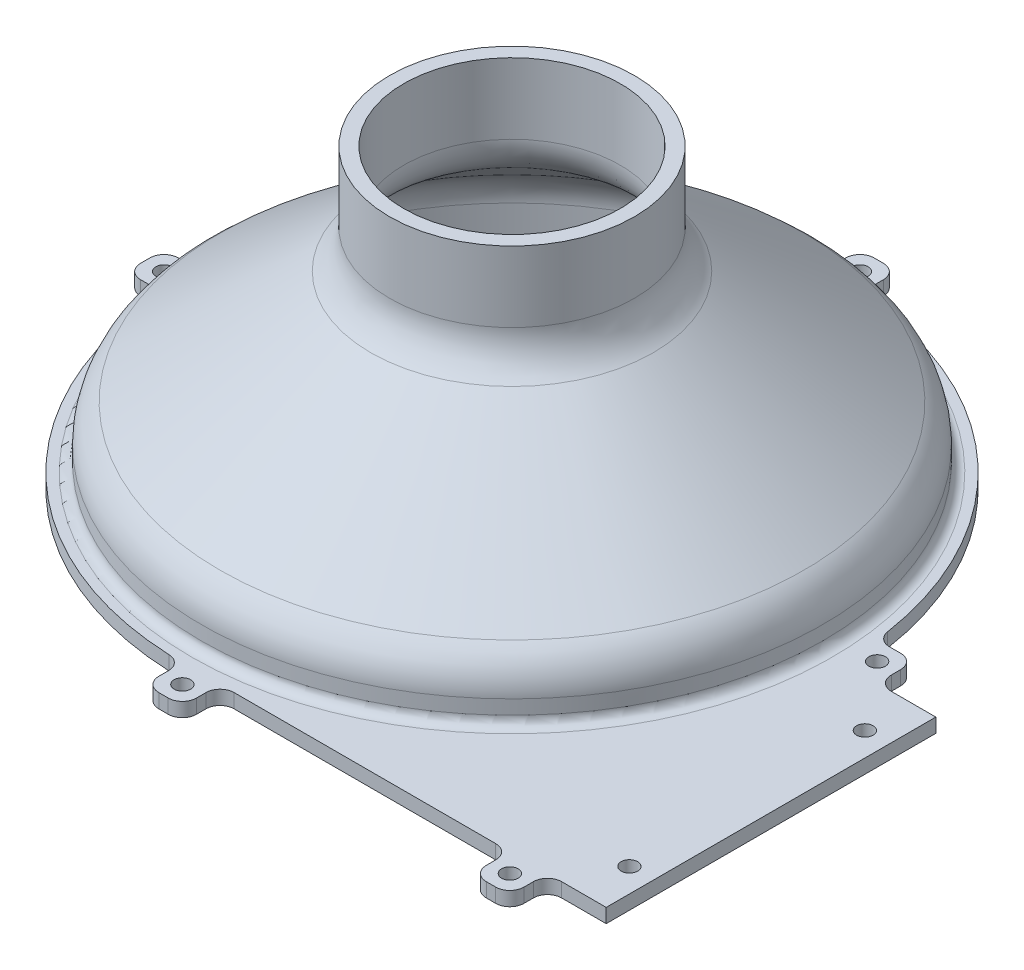
SolidWorks part; units mm, degrees
ref_plane "Front Plane" through (0, 0, 0) normal (0, 0, 1) x (1, 0, 0)
ref_plane "Top Plane" through (0, 0, 0) normal (0, 1, 0) x (1, 0, 0)
ref_plane "Right Plane" through (0, 0, 0) normal (1, 0, 0) x (0, 0, -1)
sketch "Sketch2" plane through (0, 0, 0) normal (0, 1, 0) x (1, 0, 0)
  line L0 (70, 0) -> (70, -70) construction
  line L1 (0, -70) -> (90, -70)
  line L3 (70, 0) -> (90, 0)
  line L4 (90, -70) -> (90, 0)
  arc A0 (70, 0) -> (0, -70) centre (0, 0) ccw
  circle A1 centre (0, 0) radius 63
  dimension "D1" = 140
  dimension "D4" = 126
  dimension "D3" = 20
extrude "Boss-Extrude1" add sketch "Sketch2" along normal blind 3
sketch "Sketch3" plane through (0, 3, 0) normal (0, 1, 0) x (1, 0, 0)
  circle A2 centre (0, 0) radius 63 construction
  circle A3 centre (0, 0) radius 63
  circle A4 centre (0, 0) radius 66
  dimension "D1" = 3
extrude "Boss-Extrude2" add sketch "Sketch3" along normal blind 10
sketch "Sketch6" plane through (0, 0, 0) normal (1, 0, 0) x (0, 0, -1)
  line L0 (-66, 13) -> (-26, 43)
  line L1 (-26, 43) -> (-23, 43)
  line L2 (-23, 43) -> (-63, 13)
  line L3 (66, 13) -> (-66, 13) construction
  line L4 (-66, 13) -> (-63, 13)
  line L5 (0, 0) -> (0, 43) construction
  line L6 (-70, 0) -> (70, 0) construction
  line L7 (-23, 43) -> (0, 43) construction
  dimension "D1" = 3
  dimension "D2" = 30
  dimension "D3" = 26
revolve "Revolve1" add sketch "Sketch6" angle 360 about L5
sketch "Sketch7" plane through (0, 43, 0) normal (0, 1, 0) x (1, 0, 0)
  circle A0 centre (0, 0) radius 26
  circle A1 centre (0, 0) radius 23
  circle A2 centre (0, 0) radius 23 construction
  circle A3 centre (0, 0) radius 26 construction
extrude "Boss-Extrude3" add sketch "Sketch7" along normal blind 20
fillet "Fillet1" radius 10 4 edges at (0, 43, -23) (0, 13, -63) (0, 13, 66) (0, 43, 26)
fillet "Fillet2" radius 2 1 edges at (0, 3, 66)
sketch "Sketch8" plane through (0, 0, 0) normal (0, -1, 0) x (1, 0, 0)
  line L21 (90, 0) -> (70, 0) construction
  line L22 (77.5414, 0) -> (69.5414, 0)
  line L23 (77.5414, 0) -> (77.5414, -8)
  line L24 (77.5414, -8) -> (69.5414, -8)
  line L25 (69.5414, 0) -> (69.5414, -8)
  line L26 (73.5414, 0) -> (73.5414, -8) construction
  line L27 (0, 70) -> (90, 70) construction
  line L28 (77.5414, 70) -> (69.5414, 70)
  line L29 (77.5414, 70) -> (77.5414, 78)
  line L30 (77.5414, 78) -> (69.5414, 78)
  line L31 (69.5414, 70) -> (69.5414, 78)
  line L32 (73.5414, 78) -> (73.5414, 70) construction
  line L33 (-73.8856, 4) -> (-73.8856, -4) construction
  line L34 (-69.8856, 4) -> (-77.8856, 4)
  line L35 (-69.8856, 4) -> (-69.8856, -4)
  line L36 (-69.8856, -4) -> (-77.8856, -4)
  line L37 (-77.8856, 4) -> (-77.8856, -4)
  line L38 (0, -69.8856) -> (0, -77.8856) construction
  line L39 (-4, -69.8856) -> (4, -69.8856)
  line L40 (-4, -69.8856) -> (-4, -77.8856)
  line L41 (-4, -77.8856) -> (4, -77.8856)
  line L42 (4, -69.8856) -> (4, -77.8856)
  line L43 (4, 78) -> (4, 70) construction
  line L44 (0, 70) -> (8, 70)
  line L45 (0, 70) -> (0, 78)
  line L46 (0, 78) -> (8, 78)
  line L47 (8, 70) -> (8, 78)
  arc A23 (0, 70) -> (70, 0) centre (0, 0) ccw construction
  circle A24 centre (73.5414, -4) radius 1.75
  circle A25 centre (73.5414, 74) radius 1.75
  circle A26 centre (-73.8856, 0) radius 1.75
  circle A27 centre (0, -73.8856) radius 1.75
  circle A28 centre (4, 74) radius 1.75
  dimension "D3" = 3.5
  dimension "D5" = 3.5
  dimension "D8" = 3.5
  dimension "D11" = 3.5
  dimension "D13" = 3.5
  dimension "D1" = 8
  dimension "D2" = 8
  dimension "D4" = 8
  dimension "D6" = 8
  dimension "D7" = 8
  dimension "D9" = 8
  dimension "D10" = 8
  dimension "D12" = 8
extrude "Boss-Extrude4" add sketch "Sketch8" against normal up to surface (3 mm away) up to face at (0, 3, 68)
fillet "Fillet3" radius 3 19 edges at (77.5414, 1.5, 0) (69.5414, 1.5, -8) (77.5414, 1.5, -8) (77.5414, 1.5, 70) (77.5414, 1.5, 78) (69.5414, 1.5, 78) (69.5414, 1.5, 70) (8, 1.5, 70) (8, 1.5, 78) (0, 1.5, 78) (0, 1.5, 70) (-69.8856, 1.5, 4) (-77.8856, 1.5, 4) (-77.8856, 1.5, -4) (-69.8856, 1.5, -4) (-4, 1.5, -77.8856) (4, 1.5, -77.8856) (4, 1.5, -69.8856) (-4, 1.5, -69.8856)
sketch "Sketch9" plane through (0, 3, 0) normal (0, 1, 0) x (1, 0, 0)
  line L0 (84.93, 0) -> (84.93, -70) construction
  line L1 (90, 0) -> (80.5414, 0) construction
  line L2 (80.5414, -70) -> (90, -70) construction
  line L3 (90, -70) -> (90, 0) construction
  circle A0 centre (84.93, -10) radius 1.75
  circle A1 centre (84.93, -60) radius 1.75
  dimension "D2" = 3.5
  dimension "D3" = 3.5
  dimension "D1" = 5.07
  dimension "D4" = 10
  dimension "D5" = 10
extrude "Cut-Extrude1" cut sketch "Sketch9" against normal through all
equation "\"LoftHeight\"= 30"
